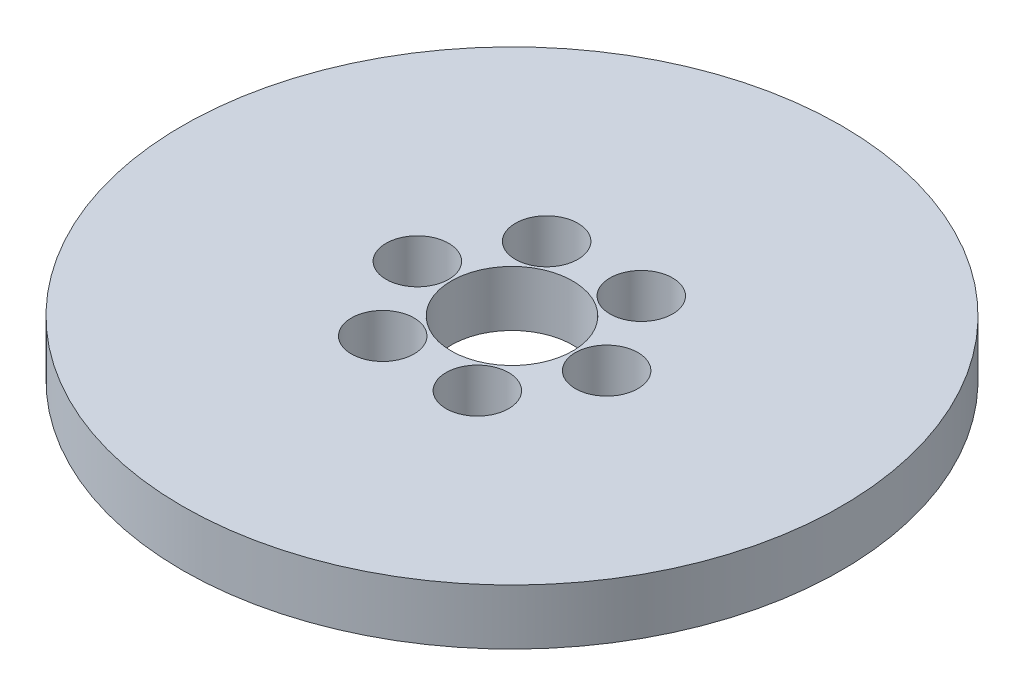
SolidWorks part; units mm, degrees
ref_plane "Front Plane" through (0, 0, 0) normal (0, 0, 1) x (1, 0, 0)
ref_plane "Top Plane" through (0, 0, 0) normal (0, 1, 0) x (1, 0, 0)
ref_plane "Right Plane" through (0, 0, 0) normal (1, 0, 0) x (0, 0, -1)
sketch "Sketch1" plane through (0, 0, 0) normal (0, 1, 0) x (1, 0, 0)
  circle A0 centre (0, 0) radius 95
  dimension "FLANGE_OD" = 190
extrude "Boss-Extrude1" add sketch "Sketch1" along normal blind 16
sketch "Sketch2" plane through (0, 0, 0) normal (0, 1, 0) x (1, 0, 0)
  circle A0 centre (0, 0) radius 17.5
  dimension "BORE_D" = 35
extrude "Cut-Extrude1" cut sketch "Sketch2" along normal through all
sketch "Sketch3" plane through (0, 16, 0) normal (0, 1, 0) x (1, 0, 0)
  circle A0 centre (0, 0) radius 27.2835 construction
  circle A1 centre (-27.2835, 0) radius 9.0213
  dimension "BOLT_D" = 18.0427
  dimension "BOLT_PCD" = 54.5669
extrude "Cut-Extrude2" cut sketch "Sketch3" against normal blind 15.9393
pattern_circular "CirPattern1" count 6 over 360 about axis through (0, 0, 0) along (0, 1, 0) of "Cut-Extrude2"
